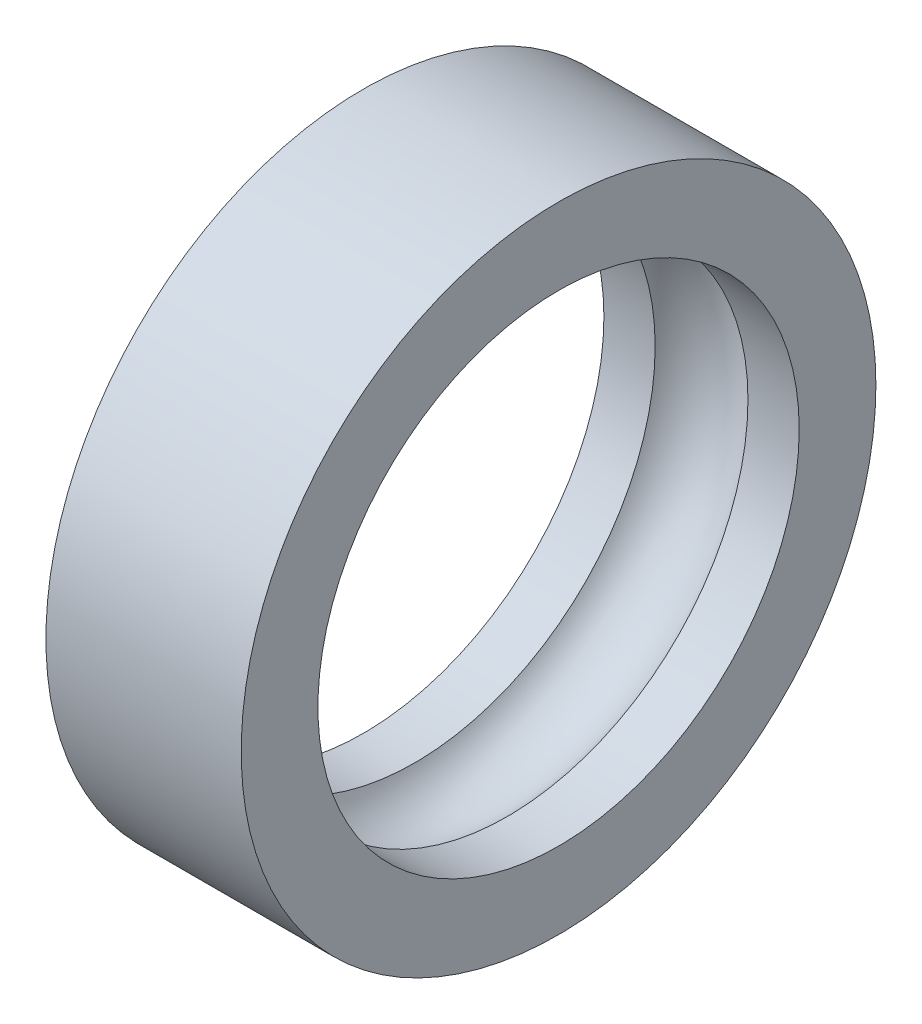
SolidWorks part; units mm, degrees
ref_plane "Front Plane" through (0, 0, 0) normal (0, 0, 1) x (1, 0, 0)
ref_plane "Top Plane" through (0, 0, 0) normal (0, 1, 0) x (1, 0, 0)
ref_plane "Right Plane" through (0, 0, 0) normal (1, 0, 0) x (0, 0, -1)
sketch "Sketch1" plane through (0, 0, 0) normal (0, 0, 1) x (1, 0, 0)
  line L0 (0, 0) -> (13.3111, 0) construction
  line L1 (13.3111, 0) -> (13.3111, 1.108) construction
  line L2 (0, 0) -> (0, 4.25) construction
  line L3 (0, 4.25) -> (4, 4.25)
  line L4 (0, 4.25) -> (-4, 4.25)
  line L5 (4, 4.25) -> (4, 1.108)
  line L6 (-4, 4.25) -> (-4, 1.108)
  line L7 (-4, 1.108) -> (-1.9006, 1.108)
  line L8 (4, 1.108) -> (1.9006, 1.108)
  line L9 (4, 4.25) -> (4, -8.75) construction
  line L10 (4, -8.75) -> (-4, -8.75) construction
  arc A0 (1.9006, 1.108) -> (-1.9006, 1.108) centre (0, 0) ccw
  dimension "D1" = 4.4
  dimension "D2" = 1.108
  dimension "D3" = 4.25
  dimension "D4" = 4
  dimension "D5" = 4
  dimension "D6" = 3.142
  dimension "D7" = 13
revolve "Revolve1" add sketch "Sketch1" angle 360 about L10
scale "Scale1" [suppressed]
scale "Scale2" scale about centroid uniform scaling yes scale factor 6
scale "Scale3" bodies to scale 106 scale about centroid uniform scaling yes scale factor 3.323882
scale "Scale4" bodies to scale 107 scale about centroid uniform scaling yes scale factor 0.416653
scale "Scale5" bodies to scale 108 scale about centroid uniform scaling yes scale factor 0.705392
scale "Scale6" bodies to scale 109 scale about centroid uniform scaling yes scale factor 0.666667
